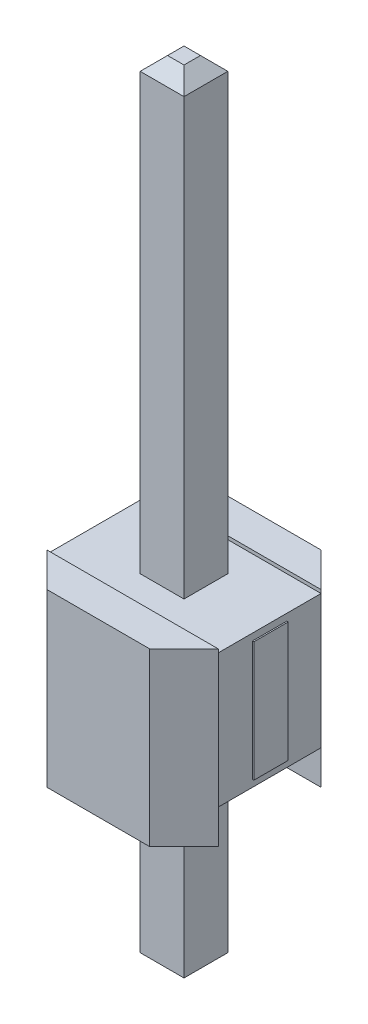
SolidWorks part; units mm, degrees
ref_plane "Front Plane" through (0, 0, 0) normal (0, 0, 1) x (1, 0, 0)
ref_plane "Top Plane" through (0, 0, 0) normal (0, 1, 0) x (1, 0, 0)
ref_plane "Right Plane" through (0, 0, 0) normal (1, 0, 0) x (0, 0, -1)
sketch "Sketch1" plane through (0, 0, 0) normal (1, 0, 0) x (0, 0, -1)
  line L1 (0, 8.07) -> (0, -3.79) construction
  line L3 (-0.32, 7.75) -> (-0.32, -3.79)
  line L5 (0.32, 7.75) -> (0.32, -3.79)
  line L7 (-0.32, -3.79) -> (0.32, -3.79)
  line L8 (-0.32, 7.75) -> (0.32, 7.75)
  line L9 (0.32, 8.39) -> (0.32, -3.79) construction
  line L10 (-7.25, 8.39) -> (0.32, 8.39) construction
  line L11 (-7.25, 8.07) -> (0, 8.07) construction
  line L12 (-7.25, 7.75) -> (-0.32, 7.75) construction
  dimension "D1" = 3.79
  dimension "D2" = 7.75
  dimension "D3" = 0.32
  dimension "D4" = 0.32
extrude "Boss-Extrude1" add sketch "Sketch1" along normal mid plane 0.64
sketch "Sketch2" plane through (0, 0, 0) normal (1, 0, 0) x (0, -1, 0)
  line L1 (-1.25, 1.25) -> (1.25, 1.25)
  line L2 (-1.25, 1.25) -> (-1.25, -1.25) construction
  line L3 (-1.25, -1.25) -> (1.25, -1.25)
  line L4 (1.25, 1.25) -> (1.25, -1.25) construction
  line L10 (1.25, 0.75) -> (1.25, 1.25)
  line L11 (1.25, 0.75) -> (0.75, 0.75)
  line L13 (1.25, -0.75) -> (0.75, -0.75)
  line L14 (0.75, 0.75) -> (0.75, -0.75)
  line L15 (1.25, -0.75) -> (1.25, -1.25)
  line L16 (-1.25, 1.25) -> (-1.25, 0.75)
  line L17 (-1.25, 0.75) -> (-1.2, 0.75)
  line L19 (-1.25, -0.75) -> (-1.2, -0.75)
  line L20 (-1.2, 0.75) -> (-1.2, -0.75)
  line L21 (-1.25, -0.75) -> (-1.25, -1.25)
  dimension "D1" = 0.5
  dimension "D2" = 2.5
  dimension "D3" = 2.5
  dimension "D4" = 0.5
  dimension "D5" = 0.5
  dimension "D6" = 1.25
  dimension "D7" = 1.25
  dimension "D8" = 0.05
extrude "Boss-Extrude3" add sketch "Sketch2" along normal mid plane 2.5 contours L14 L13 L15 L3 L21 L19 L20 L17 L16 L1 L10 L11
chamfer "Chamfer1" distance 0.5 angle 45 4 edges at (1.25, 0, 1.25) (1.25, 0, -1.25) (-1.25, 0, 1.25) (-1.25, 0, -1.25)
sketch "Sketch3" plane through (0, 0, 0) normal (1, 0, 0) x (0, 0, -1)
  line L1 (-0.25, 1.1) -> (0.25, 1.1)
  line L2 (-0.25, 1.1) -> (-0.25, -0.65)
  line L3 (-0.25, -0.65) -> (0.25, -0.65)
  line L4 (0.25, 1.1) -> (0.25, -0.65)
  dimension "D1" = 1.1
  dimension "D2" = 0.25
  dimension "D3" = 0.5
  dimension "D4" = 1.75
extrude "Boss-Extrude4" add sketch "Sketch3" along normal mid plane 2.54
chamfer "Chamfer2" distance 0.2 angle 45 8 edges at (0, -3.79, 0.32) (0.32, -3.79, 0) (0, -3.79, -0.32) (-0.32, -3.79, 0) (0, 7.75, -0.32) (0.32, 7.75, 0) (0, 7.75, 0.32) (-0.32, 7.75, 0)
ref_point "Point1"
ref_point "Point2"
ref_axis "Axis1" through (0, 7.75, 0) along (0, -1, 0)
